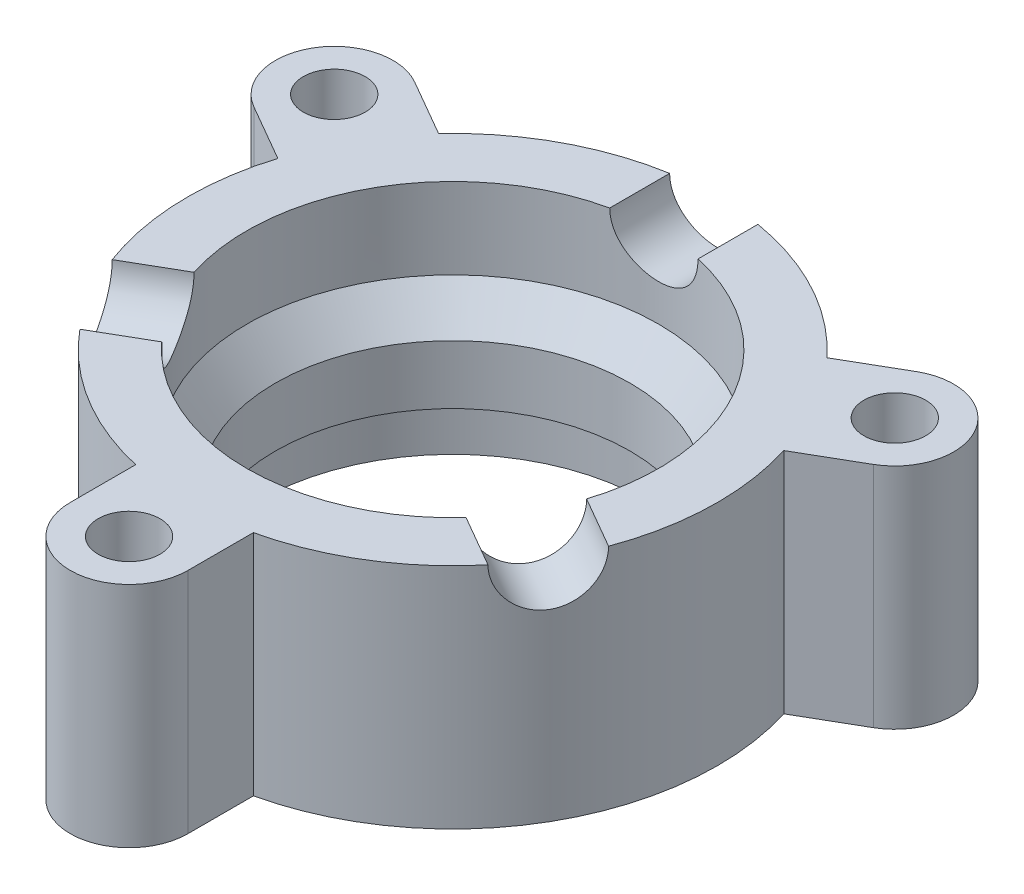
SolidWorks part; units mm, degrees
ref_plane "Front Plane" through (0, 0, 0) normal (0, 0, 1) x (1, 0, 0)
ref_plane "Top Plane" through (0, 0, 0) normal (0, 1, 0) x (1, 0, 0)
ref_plane "Right Plane" through (0, 0, 0) normal (1, 0, 0) x (0, 0, -1)
sketch "Sketch1" plane through (0, 0, 0) normal (0, 1, 0) x (1, 0, 0)
  line L0 (-4, -22) -> (-4, -17.5499)
  line L1 (4, -22) -> (4, -17.5499)
  line L2 (-21.0526, 7.5359) -> (-17.1987, 5.3109)
  line L3 (-17.0526, 14.4641) -> (-13.1987, 12.2391)
  line L4 (17.0526, 14.4641) -> (13.1987, 12.2391)
  line L5 (21.0526, 7.5359) -> (17.1987, 5.3109)
  circle A0 centre (0, 0) radius 18
  circle A1 centre (0, -22) radius 4
  circle A2 centre (0, -22) radius 2.1
  circle A3 centre (-19.0526, 11) radius 4
  circle A4 centre (-19.0526, 11) radius 2.1
  circle A5 centre (19.0526, 11) radius 4
  circle A6 centre (19.0526, 11) radius 2.1
  point P26 (0, 0)
  dimension "D1" = 36
  dimension "D2" = 8
  dimension "D4" = 4.2
  dimension "D3" = 22
  dimension "D5" = 3
extrude "Boss-Extrude1" add sketch "Sketch1" along normal blind 15.5 contours A0 | A1 L1 A0 | A1 A2 | A1 A0 L0 | A3 A0 L3 | A3 L2 A0 | A3 A4 | A5 A6 | A5 A0 L5 | A5 L4 A0 region at (-2.7484, 0, 19.2516) region at (-3.0911, 0, 18.7412) region at (0, 0, 0) region at (3.0911, 0, 18.7412) region at (-17.7759, 0, -6.6936) region at (-22.4187, 0, -12.9434) region at (-14.6848, 0, -12.0476) region at (17.7759, 0, -6.6936) region at (14.6848, 0, -12.0476) region at (18.0466, 0, -7.2456)
sketch "Sketch2" plane through (0, 15.5, 0) normal (0, 1, 0) x (1, 0, 0)
  circle A0 centre (0, 0) radius 14
  dimension "D1" = 28
extrude "Cut-Extrude1" cut sketch "Sketch2" against normal through all
sketch "Sketch3" plane through (0, 0, 0) normal (0, 0, 1) x (1, 0, 0)
  line L0 (14, 10) -> (12.0587, 7.5)
  line L1 (12.0587, 7.5) -> (12.0587, 3.5)
  line L2 (12.0587, 3.5) -> (13.1987, 3.5)
  line L3 (13.1987, 3.5) -> (13.1987, 0)
  line L4 (13.1987, 0) -> (14, 0)
  line L5 (-14, 0) -> (14, 0) construction
  line L6 (14, 0) -> (14, 10) construction
  line L7 (14, 15.5) -> (-14, 15.5) construction
  line L8 (14, 10) -> (14.4992, 10)
  line L9 (14.4992, 10) -> (14.4992, 0)
  line L10 (14.4992, 0) -> (14, 0)
  point P12 (0, 0)
  dimension "D1" = 5.5
  dimension "D2" = 2.5
  dimension "D3" = 4
  dimension "D4" = 1.14
ref_axis "Axis1" through (0, 0, 0) along (0, 1, 0)
revolve "Revolve1" add sketch "Sketch3" angle 360 about axis through (0, 0, 0) along (0, 1, 0)
sketch "Sketch4" plane through (0, 0, 0) normal (0, 0, 1) x (1, 0, 0)
  line L0 (13.1987, 15.5) -> (-13.1987, 15.5) construction
  circle A0 centre (0, 15.5) radius 3
  point P2 (0, 0)
  point P5 (0, 0)
  dimension "D1" = 6
extrude "Cut-Extrude2" cut sketch "Sketch4" against normal up to surface (17.7482 mm away) up to face at (0, 7.75, -15.1195)
pattern_circular "CirPattern1" count 3 over 360 about axis through (0, 0, 0) along (0, 1, 0) of "Cut-Extrude2"
